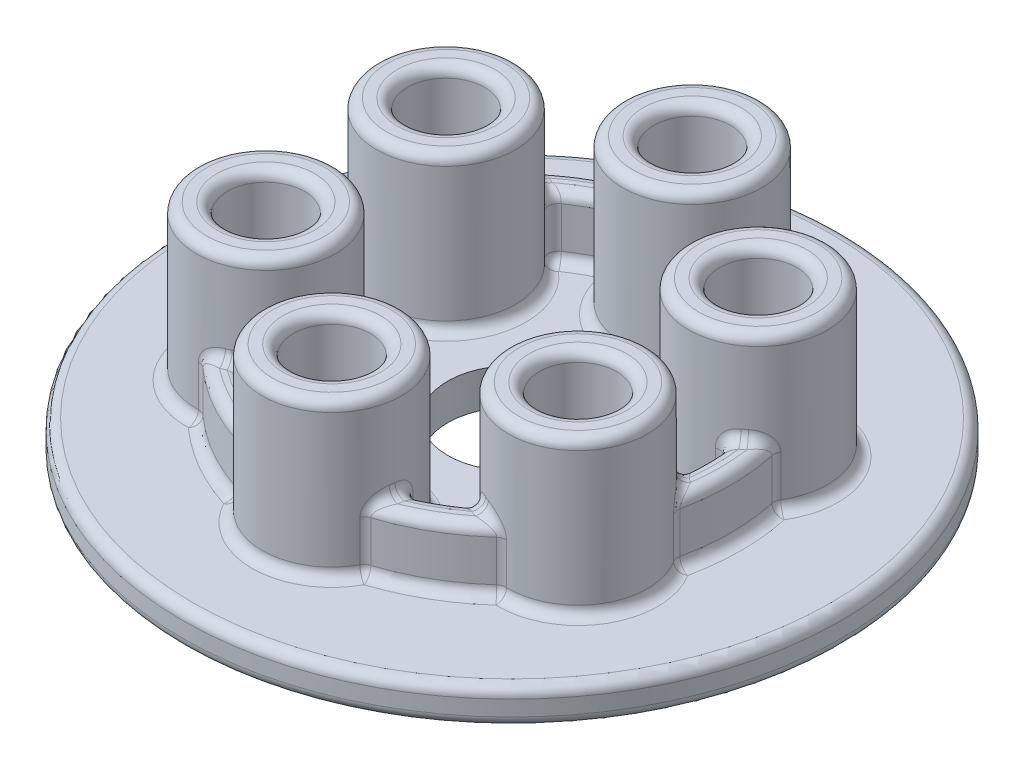
SolidWorks part; units mm, degrees
ref_plane "Front Plane" through (0, 0, 0) normal (0, 0, 1) x (1, 0, 0)
ref_plane "Top Plane" through (0, 0, 0) normal (0, 1, 0) x (1, 0, 0)
ref_plane "Right Plane" through (0, 0, 0) normal (1, 0, 0) x (0, 0, -1)
sketch "Sketch1" plane through (0, 0, 0) normal (0, 1, 0) x (1, 0, 0)
  circle A0 centre (0, 0) radius 64
  dimension "D1" = 128
extrude "Boss-Extrude1" add sketch "Sketch1" along normal blind 7
sketch "Sketch2" plane through (0, 7, 0) normal (0, 1, 0) x (1, 0, 0)
  circle A0 centre (0, 0) radius 37.5
  circle A1 centre (0, 0) radius 42.5
  dimension "D1" = 75
  dimension "D2" = 5
extrude "Boss-Extrude2" add sketch "Sketch2" along normal blind 12
sketch "Sketch3" plane through (0, 7, 0) normal (0, 1, 0) x (1, 0, 0)
  circle A0 centre (0, 0) radius 12.5
  dimension "D1" = 25
extrude "Cut-Extrude1" cut sketch "Sketch3" against normal through all
fillet "Fillet1" radius 2 4 edges at (0, 0, 64) (0, 7, 64) (0, 19, 37.5) (0, 19, 42.5)
sketch "Sketch4" plane through (0, 7, 0) normal (0, 1, 0) x (1, 0, 0)
  line L0 (0, 0) -> (0, -35) construction
  circle A0 centre (0, -35) radius 13.5
  dimension "D1" = 27
  dimension "D2" = 35
extrude "Boss-Extrude3" add sketch "Sketch4" along normal blind 30
sketch "Sketch5" plane through (0, 37, 0) normal (0, 1, 0) x (1, 0, 0)
  circle A0 centre (0, -35) radius 7.5
  dimension "D1" = 15
extrude "Cut-Extrude2" cut sketch "Sketch5" against normal through all
fillet "Fillet2" radius 2 13 edges at (13.5, 12, 34.9857) (13.494, 18.1807, 35.4011) (13.2149, 19, 37.7597) (12.5545, 18.4391, 39.9632) (-13.5, 12, 34.9857) (-13.4844, 18.4416, 35.6487) (-13.2149, 19, 37.7597) (-12.3921, 18.0279, 40.3559) (0, 37, 48.5) (0, 37, 42.5) (12.2376, 12, 40.7) (-12.2376, 12, 40.7) (0, 0, 42.5)
pattern_circular "CirPattern1" count 6 over 360 about axis through (0, 19, 0) along (0, -1, 0) of "Fillet2", "Cut-Extrude2", "Boss-Extrude3"
fillet "Fillet3" radius 2 48 edges at (14.3172, 7, 33.8557) (18.75, 7, 32.476) (22.1613, 7, 29.3269) (18.6195, 7, 10.75) (36.4785, 7, 4.5288) (37.5, 7, 0) (36.4785, 7, -4.5288) (18.6195, 7, -10.75) (22.1613, 7, -29.3269) (18.75, 7, -32.476) (14.3172, 7, -33.8557) (0, 7, -21.5) (-14.3172, 7, -33.8557) (-18.75, 7, -32.476) (-22.1613, 7, -29.3269) (-18.6195, 7, -10.75) (-36.4785, 7, -4.5288) (-37.5, 7, 0) (-36.4785, 7, 4.5288) (-18.6195, 7, 10.75) (-22.1613, 7, 29.3269) (-18.75, 7, 32.476) (-14.3172, 7, 33.8557) (-29.1691, 7, -31.117) (-21.25, 7, -36.8061) (-12.3636, 7, -40.8196) (0, 7, -48.5) (12.3636, 7, -40.8196) (21.25, 7, -36.8061) (29.1691, 7, -31.117) (42.0022, 7, -24.25) (41.5326, 7, -9.7027) (42.5, 7, 0) (41.5326, 7, 9.7027) (42.0022, 7, 24.25) (29.1691, 7, 31.117) (21.25, 7, 36.8061) (12.3636, 7, 40.8196) (0, 7, 48.5) (-12.3636, 7, 40.8196) (-21.25, 7, 36.8061) (-29.1691, 7, 31.117) (-42.0022, 7, 24.25) (-41.5326, 7, 9.7027) (-42.5, 7, 0) (-41.5326, 7, -9.7027) (0, 7, 21.5) (-42.0022, 7, -24.25)
